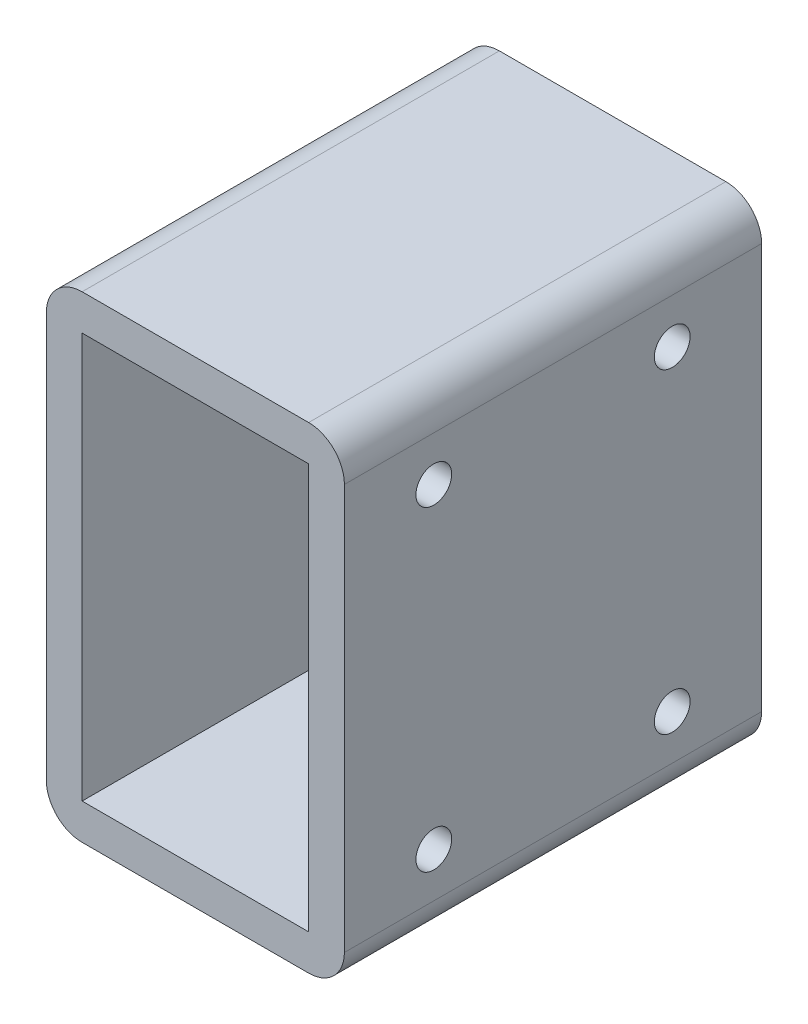
SolidWorks part; units mm, degrees
ref_plane "Front Plane" through (0, 0, 0) normal (0, 0, 1) x (1, 0, 0)
ref_plane "Top Plane" through (0, 0, 0) normal (0, 1, 0) x (1, 0, 0)
ref_plane "Right Plane" through (0, 0, 0) normal (1, 0, 0) x (0, 0, -1)
sketch "Sketch1" plane through (0, 0, 0) normal (0, 0, 1) x (1, 0, 0)
  line L0 (19, 34) -> (-19, 34)
  line L1 (19, -40) -> (-19, -40)
  line L2 (25, -34) -> (25, 34)
  line L3 (19, 40) -> (-19, 40)
  line L4 (-25, -34) -> (-25, 34)
  line L5 (25, -40) -> (-25, 40) construction
  line L6 (25, 40) -> (-25, -40) construction
  line L7 (-19, -34) -> (-19, 34)
  line L8 (19, -34) -> (-19, -34)
  line L9 (19, -34) -> (19, 34)
  arc A0 (-19, -40) -> (-25, -34) centre (-19, -34) cw
  arc A1 (19, -40) -> (25, -34) centre (19, -34) ccw
  arc A2 (25, 34) -> (19, 40) centre (19, 34) ccw
  arc A3 (-19, 40) -> (-25, 34) centre (-19, 34) ccw
  arc A4 (-19, 34) -> (-19, 34) centre (-19, 34) ccw
  arc A5 (-19, -34) -> (-19, -34) centre (-19, -34) cw
  arc A6 (19, -34) -> (19, -34) centre (19, -34) ccw
  arc A7 (19, 34) -> (19, 34) centre (19, 34) ccw
  point P0 (0, 0)
  dimension "D1" = 6
  dimension "D3" = 80
  dimension "D4" = 50
  dimension "D2" = 6
extrude "Boss-Extrude1" add sketch "Sketch1" along normal mid plane 70
sketch "Sketch2" plane through (25, 0, 0) normal (1, 0, 0) x (0, 0, -1)
  line L1 (20, -26.5) -> (-20, -26.5) construction
  line L2 (20, -26.5) -> (20, 26.5) construction
  line L3 (20, 26.5) -> (-20, 26.5) construction
  line L4 (-20, -26.5) -> (-20, 26.5) construction
  line L5 (20, -26.5) -> (-20, 26.5) construction
  line L6 (20, 26.5) -> (-20, -26.5) construction
  circle A0 centre (-20, 26.5) radius 3
  circle A1 centre (20, 26.5) radius 3
  circle A2 centre (20, -26.5) radius 3
  circle A3 centre (-20, -26.5) radius 3
  point P0 (0, 0)
  dimension "D3" = 6
  dimension "D1" = 40
  dimension "D2" = 53
extrude "Cut-Extrude1" cut sketch "Sketch2" against normal blind 10
equation "\"M5_tap\"=4.2mm"
equation "\"M5_clearence\"=5.5mm"
equation "\"M6_tap\"=5mm"
equation "\"M6_clearence\"=6.6mm"
equation "\"work_area_width\"=1100mm"
equation "\"work_area_depth\"=900mm"
equation "\"D3@Sketch1\"=\"steel_rollers_width\""
equation "\"D4@Sketch1\"=\"steel_rollers_height\""
equation "\"D1@Sketch1\"=\"steel_rollers_radius\""
equation "\"D2@Sketch1\"=\"steel_rollers_wall_thickness\""
equation "\"D1@Boss-Extrude1\"=\"work_area_depth\" + 200"
equation "\"steel_base_width\"=80mm"
equation "\"steel_base_height\"=50mm"
equation "\"steel_base_wall_thickness\"=3mm"
equation "\"steel_base_radius\"=6mm"
equation "\"steel_sides_width\"=80mm"
equation "\"steel_sides_height\"=50mm"
equation "\"steel_sides_wall_thickness\"=5mm"
equation "\"steel_sides_radius\"=6mm"
equation "\"steel_gantry_width\"=80mm"
equation "\"steel_gantry_height\"=50mm"
equation "\"steel_gantry_wall_thickness\"=6mm"
equation "\"steel_gantry_radius\"=6mm"
equation "\"steel_rollers_width\"=80mm"
equation "\"steel_rollers_height\"=50mm"
equation "\"steel_rollers_wall_thickness\"=6mm"
equation "\"steel_rollers_radius\"=6mm"
equation "\"steel_zbox_width\"=80mm"
equation "\"steel_zbox_height\"=50mm"
equation "\"steel_zbox_wall_thickness\"=3mm"
equation "\"steel_zbox_radius\"=6mm"
